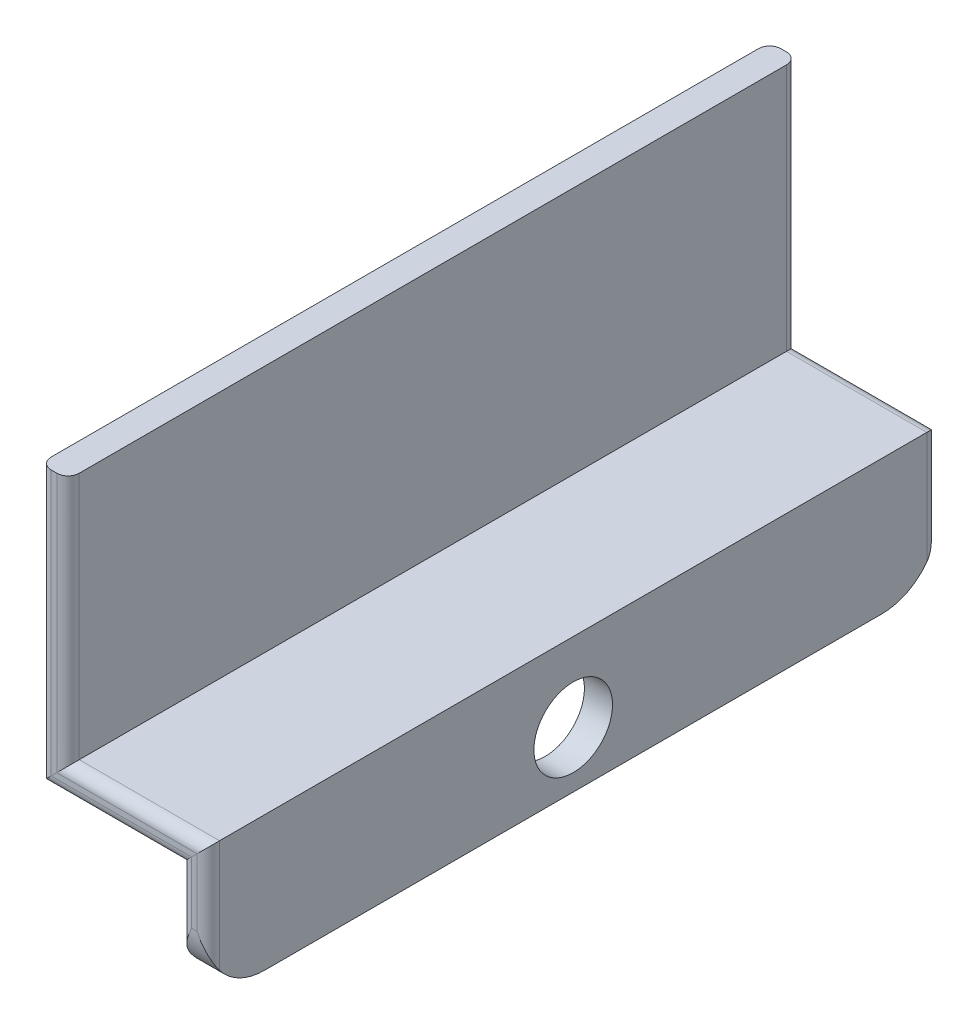
SolidWorks part; units mm, degrees
ref_plane "Front Plane" through (0, 0, 0) normal (0, 0, 1) x (1, 0, 0)
ref_plane "Top Plane" through (0, 0, 0) normal (0, 1, 0) x (1, 0, 0)
ref_plane "Right Plane" through (0, 0, 0) normal (1, 0, 0) x (0, 0, -1)
sketch3d "3DSketch1"
  line L0 (0, 0, 0) -> (0, 21.5, 0)
  line L1 (0, 21.5, 0) -> (-25, 21.5, 0)
  line L2 (-25, 21.5, 0) -> (-25, 68.2, 0)
  line L3 (-25, 68.2, 0) -> (39.395, 68.2, 0) construction
  dimension "D1" = 25
  dimension "D2" = 46.7
  dimension "D3" = 21.5
sketch "Sketch2" plane through (0, 0, 0) normal (0, 1, 0) x (1, 0, 0)
  line L1 (-0.5, 65) -> (0.5, 65)
  line L2 (-2.5, 63) -> (-2.5, -63)
  line L3 (-0.5, -65) -> (0.5, -65)
  line L4 (2.5, 63) -> (2.5, -63)
  line L5 (-2.5, 65) -> (2.5, -65) construction
  line L6 (-2.5, -65) -> (2.5, 65) construction
  arc A0 (0.5, 65) -> (2.5, 63) centre (0.5, 63) cw
  arc A1 (2.5, -63) -> (0.5, -65) centre (0.5, -63) cw
  arc A2 (-0.5, -65) -> (-2.5, -63) centre (-0.5, -63) cw
  arc A3 (-2.5, 63) -> (-0.5, 65) centre (-0.5, 63) cw
  point P0 (0, 0)
  dimension "D3" = 2
  dimension "D1" = 130
  dimension "D2" = 5
sketch "Sketch3" plane through (0, 0, 0) normal (1, 0, 0) x (0, 0, -1)
  line L0 (0, 0) -> (0, 21.5) construction
  circle A0 centre (0, 10) radius 7
  dimension "D1" = 14
  dimension "D2" = 10
sweep "Sweep1" add profiles "Sketch2" path "3DSketch1"
extrude "Cut-Extrude1" cut sketch "Sketch3" against normal through all both and the other way through all
fillet "Fillet2" radius 10 3 edges at (-1.9142, 0, -64.4142) (1.9142, 0, -64.4142) (0, 0, -65)
fillet "Fillet3" radius 10 3 edges at (-1.9142, 0, 64.4142) (0, 0, 65) (1.9142, 0, 64.4142)
